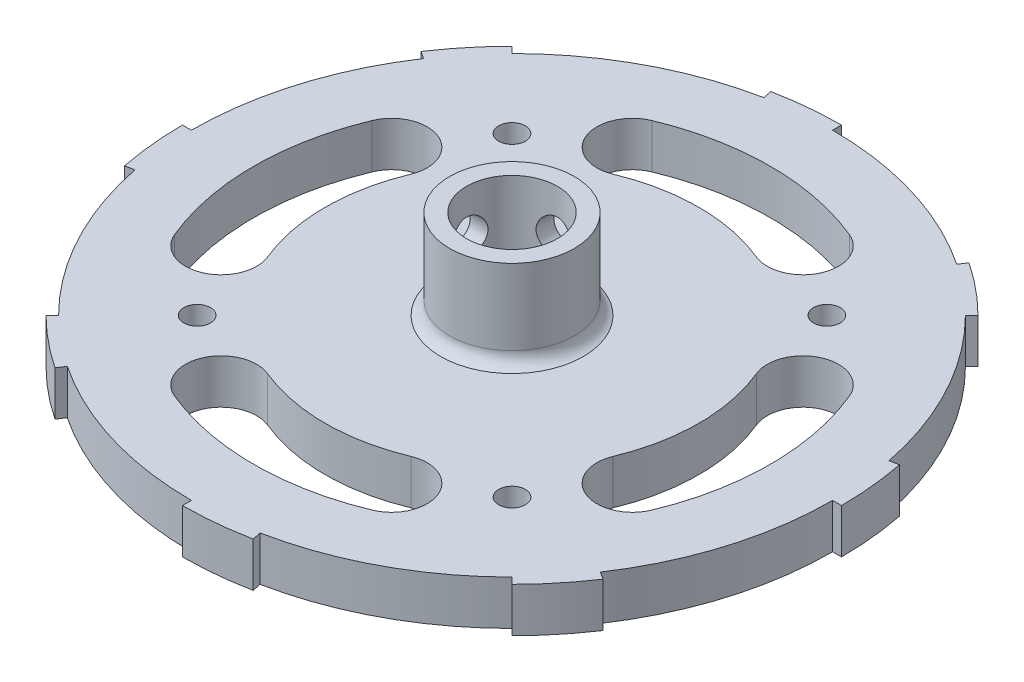
SolidWorks part; units mm, degrees
ref_plane "前视基准面" through (0, 0, 0) normal (0, 0, 1) x (1, 0, 0)
ref_plane "上视基准面" through (0, 0, 0) normal (0, 1, 0) x (1, 0, 0)
ref_plane "右视基准面" through (0, 0, 0) normal (1, 0, 0) x (0, 0, -1)
other "Configuration Table"
sketch "草图1" plane through (0, 0, 0) normal (0, 1, 0) x (1, 0, 0)
  circle A0 centre (0, 0) radius 37
  dimension "D1" = 74
extrude "凸台-拉伸1" add sketch "草图1" along normal blind 40
sketch "草图2" plane through (0, 40, 0) normal (0, 1, 0) x (1, 0, 0)
  circle A0 centre (0, 0) radius 5.1
  dimension "D1" = 10.2
extrude "切除-拉伸1" cut sketch "草图2" against normal blind 40
sketch "草图3" plane through (0, 40, 0) normal (0, 1, 0) x (1, 0, 0)
  line L0 (-1000, 0) -> (49000, 0) construction
  line L1 (0, -1000) -> (0, 49000) construction
  circle A0 centre (0, 0) radius 30
  circle A1 centre (0, 30) radius 5
  circle A3 centre (25.9808, 15) radius 5
  circle A4 centre (30, 0) radius 5
  circle A5 centre (25.9808, -15) radius 5
  circle A7 centre (0, -30) radius 5
  circle A8 centre (-15, -25.9808) radius 5
  circle A9 centre (-25.9808, -15) radius 5
  circle A11 centre (-25.9808, 15) radius 5
  circle A12 centre (-15, 25.9808) radius 5
  circle A13 centre (0, 0) radius 25
  circle A14 centre (0, 0) radius 35
  circle A15 centre (-30, 0) radius 5 [skipped]
  circle A16 centre (15, -25.9808) radius 5 [skipped]
  circle A17 centre (15, 25.9808) radius 5 [skipped]
  point P34 (0, 0)
  dimension "D1" = 60
  dimension "D2" = 10
  dimension "D3" = 12
extrude "切除-拉伸2" cut sketch "草图3" against normal blind 40 contours A0 A11 | A0 A11 | A13 A12 A0 A11 | A12 A14 A11 A0 | A0 A12 | A0 A12 | A1 A14 A12 A0 | A13 A1 A0 A12 | A0 A1 | A0 A1 | A0 A9 | A0 A9 | A9 A14 A8 A0 | A13 A9 A0 A8 | A0 A8 | A0 A8 | A8 A14 A7 A0 | A13 A8 A0 A7 | A0 A7 | A0 A7 | A0 A5 | A0 A5 | A0 A4 | A0 A4 | A0 A3 | A0 A3 | A4 A14 A3 A0 | A13 A4 A0 A3 | A13 A5 A0 A4 | A5 A14 A4 A0 region at (27.8047, 40, 0) region at (32.0453, 40, 0) region at (26.1943, 40, -7.0188) region at (31.6944, 40, -8.4925) region at (31.6944, 40, 8.4925) region at (26.1943, 40, 7.0188) region at (24.0795, 40, -13.9023) region at (27.752, 40, -16.0226) region at (27.752, 40, 16.0226) region at (24.0795, 40, 13.9023) region at (-7.0188, 40, -26.1943) region at (0, 40, -27.8047) region at (0, 40, -32.0453) region at (-8.4925, 40, -31.6944) region at (-8.4925, 40, 31.6944) region at (0, 40, 32.0453) region at (0, 40, 27.8047) region at (-7.0188, 40, 26.1943) region at (-19.1756, 40, -19.1756) region at (-13.9023, 40, -24.0795) region at (-16.0226, 40, -27.752) region at (-23.2019, 40, -23.2019) region at (-23.2019, 40, 23.2019) region at (-16.0226, 40, 27.752) region at (-13.9023, 40, 24.0795) region at (-19.1756, 40, 19.1756) region at (-24.0795, 40, -13.9023) region at (-27.752, 40, -16.0226) region at (-27.752, 40, 16.0226) region at (-24.0795, 40, 13.9023)
sketch "草图4" plane through (0, 40, 0) normal (0, 1, 0) x (1, 0, 0)
  circle A0 centre (0, 0) radius 7
  circle A1 centre (0, 0) radius 5.1
  dimension "D1" = 14
extrude "凸台-拉伸2" add sketch "草图4" along normal mid plane 20
sketch "草图5" plane through (0, 0, 0) normal (0, -1, 0) x (1, 0, 0)
  circle A0 centre (0, 0) radius 5.1
sketch "草图6" plane through (0, 0, 0) normal (0, 0, 1) x (1, 0, 0)
  line L0 (0, 50) -> (0, 45)
  line L1 (5.1, 50) -> (-5.1, 50) construction
  circle A0 centre (0, 45) radius 2
  dimension "D2" = 4
  dimension "D1" = 5
extrude "切除-拉伸3" cut sketch "草图6" against normal up to next contours A0 region at (-1.3742, 43.6258, 0)
sketch "草图7" plane through (0, 0, 0) normal (1, 0, 0) x (0, 0, -1)
  line L0 (0, 50) -> (0, 45)
  line L1 (7, 50) -> (-7, 50) construction
  circle A0 centre (0, 45) radius 2
  dimension "D2" = 4
  dimension "D1" = 5
extrude "切除-拉伸4" cut sketch "草图7" against normal up to next contours A0 region at (0, 43.6258, 1.3742)
sketch "草图10" plane through (0, 0, 0) normal (0, -1, 0) x (1, 0, 0)
  line L0 (0, 0) -> (0, 37)
  line L1 (0, 0) -> (7.2183, 36.2891)
  line L2 (0, 0) -> (14.1593, 34.1835)
  line L3 (0, 0) -> (20.5561, 30.7644)
  line L4 (0, 0) -> (26.163, 26.163)
  line L5 (0, 0) -> (30.7644, 20.5561)
  line L6 (0, 0) -> (34.1835, 14.1593)
  line L7 (0, 0) -> (36.2891, 7.2183)
  line L8 (0, 0) -> (37, 0)
  line L9 (0, 0) -> (36.2891, -7.2183)
  line L10 (0, 0) -> (34.1835, -14.1593)
  line L11 (0, 0) -> (30.7644, -20.5561)
  line L12 (0, 0) -> (26.163, -26.163)
  line L13 (0, 0) -> (20.5561, -30.7644)
  line L14 (0, 0) -> (14.1593, -34.1835)
  line L15 (0, 0) -> (7.2183, -36.2891)
  line L16 (0, 0) -> (0, -37)
  line L17 (0, 0) -> (-7.2183, -36.2891)
  line L18 (0, 0) -> (-14.1593, -34.1835)
  line L19 (0, 0) -> (-20.5561, -30.7644)
  line L20 (0, 0) -> (-26.163, -26.163)
  line L21 (0, 0) -> (-30.7644, -20.5561)
  line L22 (0, 0) -> (-34.1835, -14.1593)
  line L23 (0, 0) -> (-36.2891, -7.2183)
  line L24 (0, 0) -> (-37, 0)
  line L25 (0, 0) -> (-36.2891, 7.2183)
  line L26 (0, 0) -> (-34.1835, 14.1593)
  line L27 (0, 0) -> (-30.7644, 20.5561)
  line L28 (0, 0) -> (-26.163, 26.163)
  line L29 (0, 0) -> (-20.5561, 30.7644)
  line L30 (0, 0) -> (-14.1593, 34.1835)
  line L31 (0, 0) -> (-7.2183, 36.2891)
  circle A0 centre (0, 0) radius 37
  circle A1 centre (0, 0) radius 36
  point P38 (0, 0)
  circle M14 centre (0, 0) radius 37
  dimension "D1" = 72
  dimension "D2" = 37
  dimension "D3" = 32
extrude "切除-拉伸7" cut sketch "草图10" against normal up to next contours A1 L26 L25 M14 | A1 L27 L26 M14 | A1 L28 L27 M14 | A1 L30 L29 M14 | A1 L31 L30 M14 | A1 L0 L31 M14 | A1 L2 L1 M14 | A1 L3 L2 M14 | A1 L4 L3 M14 | A1 L6 L5 M14 | A1 L7 L6 M14 | A1 L8 L7 M14 | A1 L10 L9 M14 | A1 L11 L10 M14 | A1 L12 L11 M14 | A1 L14 L13 M14 | A1 L15 L14 M14 | A1 L16 L15 M14 | A1 L18 L17 M14 | A1 L19 L18 M14 | A1 L20 L19 M14 | A1 L22 L21 M14 | A1 L23 L22 M14 | A1 L24 L23 M14 region at (-3.5721, 0, 36.2682) region at (10.579, 0, 34.8744) region at (17.1794, 0, 32.1405) region at (23.1196, 0, 28.1713) region at (32.1405, 0, 17.1794) region at (34.8744, 0, 10.579) region at (36.2682, 0, 3.5721) region at (34.8744, 0, -10.579) region at (32.1405, 0, -17.1794) region at (28.1713, 0, -23.1196) region at (17.1794, 0, -32.1405) region at (10.579, 0, -34.8744) region at (3.5721, 0, -36.2682) region at (-10.579, 0, -34.8744) region at (-17.1794, 0, -32.1405) region at (-23.1196, 0, -28.1713) region at (-32.1405, 0, -17.1794) region at (-34.8744, 0, -10.579) region at (-36.2682, 0, -3.5721) region at (-34.8744, 0, 10.579) region at (-32.1405, 0, 17.1794) region at (-28.1713, 0, 23.1196) region at (-17.1794, 0, 32.1405) region at (-10.579, 0, 34.8744)
sketch "草图14" plane through (0, 40, 0) normal (0, 1, 0) x (1, 0, 0)
  circle A0 centre (0, 0) radius 36
extrude "凸台-拉伸4" add sketch "草图14" against normal blind 40
sketch "草图15" plane through (0, 40, 0) normal (0, 1, 0) x (1, 0, 0)
  circle A0 centre (0, 0) radius 25
  circle A1 centre (0, 25) radius 5
  circle A2 centre (12.5, 21.6506) radius 5
  circle A3 centre (21.6506, 12.5) radius 5
  circle A4 centre (25, 0) radius 5
  circle A5 centre (21.6506, -12.5) radius 5
  circle A6 centre (12.5, -21.6506) radius 5
  circle A7 centre (0, -25) radius 5
  circle A8 centre (-12.5, -21.6506) radius 5
  circle A9 centre (-21.6506, -12.5) radius 5
  circle A10 centre (-25, 0) radius 5
  circle A11 centre (-21.6506, 12.5) radius 5
  circle A12 centre (-12.5, 21.6506) radius 5
  circle A13 centre (0, 0) radius 30
  circle A14 centre (0, 0) radius 20
  point P30 (0, 0)
  dimension "D1" = 50
  dimension "D2" = 10
  dimension "D3" = 12
extrude "切除-拉伸11" cut sketch "草图15" against normal blind 40 contours A14 A12 A0 A11 | A12 A13 A11 A0 | A0 A11 | A0 A11 | A0 A12 | A0 A12 | A0 A1 | A0 A1 | A2 A13 A1 A0 | A14 A2 A0 A1 | A0 A2 | A0 A2 | A0 A3 | A0 A3 | A14 A4 A0 A3 | A4 A13 A3 A0 | A0 A4 | A0 A4 | A0 A5 | A0 A5 | A0 A6 | A0 A6 | A14 A6 A0 A5 | A6 A13 A5 A0 | A0 A7 | A0 A7 | A0 A8 | A0 A8 | A8 A13 A7 A0 | A14 A8 A0 A7 | A0 A9 | A0 A9 | A14 A10 A0 A9 | A10 A13 A9 A0 | A0 A10 | A0 A10 region at (22.7904, 40, 0) region at (27.0295, 40, 0) region at (21.2179, 40, -5.6853) region at (27.0803, 40, -7.2562) region at (19.7371, 40, -11.3952) region at (23.4082, 40, -13.5147) region at (23.4082, 40, 13.5147) region at (19.7371, 40, 11.3952) region at (19.8242, 40, 19.8242) region at (15.5326, 40, 15.5326) region at (11.3952, 40, -19.7371) region at (13.5147, 40, -23.4082) region at (5.6853, 40, -21.2179) region at (7.2562, 40, -27.0803) region at (13.5147, 40, 23.4082) region at (11.3952, 40, 19.7371) region at (0, 40, -22.7904) region at (0, 40, -27.0295) region at (-7.2562, 40, 27.0803) region at (0, 40, 27.0295) region at (0, 40, 22.7904) region at (-5.6853, 40, 21.2179) region at (-15.5326, 40, -15.5326) region at (-11.3952, 40, -19.7371) region at (-13.5147, 40, -23.4082) region at (-19.8242, 40, -19.8242) region at (-13.5147, 40, 23.4082) region at (-11.3952, 40, 19.7371) region at (-19.7371, 40, -11.3952) region at (-23.4082, 40, -13.5147) region at (-27.0803, 40, 7.2562) region at (-23.4082, 40, 13.5147) region at (-19.7371, 40, 11.3952) region at (-21.2179, 40, 5.6853) region at (-22.7904, 40, 0) region at (-27.0295, 40, 0)
sketch "草图17" plane through (0, 40, 0) normal (0, 1, 0) x (1, 0, 0)
  circle A0 centre (0, 0) radius 5.1
extrude "切除-拉伸12" cut sketch "草图17" against normal blind 40
ref_plane "基准面2" through (0, 20, 0) normal (0, 1, 0) x (1, 0, 0)
sketch "草图18" plane through (0, 20, 0) normal (0, 1, 0) x (1, 0, 0)
  line L0 (-27.5, 0) -> (27.5, 0) construction
  circle A0 centre (0, 0) radius 37
  circle A1 centre (0, 0) radius 10
  dimension "D1" = 20
sketch "草图20" plane through (0, 0, 0) normal (0, 0, 1) x (1, 0, 0)
  line L0 (-7, 40) -> (-7, 41.5)
  line L2 (-7, 43.0001) -> (-7, 40) construction
  line L3 (0, 40) -> (-20.0005, 40) construction
  line L4 (-8.0182, 40) -> (-7, 40)
  line L5 (0, -950) -> (0, 49050) construction
  line L6 (7, 50) -> (-7, 50) construction
  arc A0 (-7, 41.5) -> (-8.0182, 40) centre (-8.6141, 41.5) cw
  point P14 (0, 50)
revolve "旋转1" add sketch "草图20" angle 360 about L5
sketch "草图21" plane through (0, 0, 0) normal (0, -1, 0) x (1, 0, 0)
  circle A0 centre (0, 0) radius 37
extrude "切除-拉伸14" cut sketch "草图21" against normal blind 35
sketch "草图23" plane through (0, 35, 0) normal (0, -1, 0) x (1, 0, 0)
  circle A0 centre (0, 0) radius 5.1
  circle A1 centre (0, 0) radius 30
extrude "凸台-拉伸5" add sketch "草图23" against normal blind 5
sketch "草图24" plane through (0, 35, 0) normal (0, -1, 0) x (1, 0, 0)
  circle A0 centre (0, 0) radius 25
  circle A1 centre (0, 25) radius 4
  circle A2 centre (9.5671, 23.097) radius 4
  circle A3 centre (17.6777, 17.6777) radius 4
  circle A4 centre (23.097, 9.5671) radius 4
  circle A5 centre (25, 0) radius 4
  circle A6 centre (23.097, -9.5671) radius 4
  circle A7 centre (17.6777, -17.6777) radius 4
  circle A8 centre (9.5671, -23.097) radius 4
  circle A9 centre (0, -25) radius 4
  circle A10 centre (-9.5671, -23.097) radius 4
  circle A11 centre (-17.6777, -17.6777) radius 4
  circle A12 centre (-23.097, -9.5671) radius 4
  circle A13 centre (-25, 0) radius 4
  circle A14 centre (-23.097, 9.5671) radius 4
  circle A15 centre (-17.6777, 17.6777) radius 4
  circle A16 centre (-9.5671, 23.097) radius 4
  circle A17 centre (0, 0) radius 29
  circle A18 centre (0, 0) radius 21
  point P37 (0, 0)
  dimension "D1" = 50
  dimension "D2" = 8
  dimension "D3" = 16
extrude "切除-拉伸15" cut sketch "草图24" against normal blind 5 contours A0 A16 | A0 A16 | A18 A1 A0 A16 | A1 A17 A16 A0 | A0 A1 | A0 A1 | A18 A2 A0 A1 | A2 A17 A1 A0 | A0 A2 | A0 A2 | A0 A4 | A0 A4 | A18 A5 A0 A4 | A5 A17 A4 A0 | A0 A5 | A0 A5 | A18 A6 A0 A5 | A6 A17 A5 A0 | A0 A6 | A0 A6 | A0 A8 | A0 A8 | A0 A9 | A0 A9 | A18 A9 A0 A8 | A9 A17 A8 A0 | A18 A10 A0 A9 | A10 A17 A9 A0 | A0 A10 | A0 A10 | A0 A12 | A0 A12 | A13 A17 A12 A0 | A18 A13 A0 A12 | A0 A13 | A0 A13 | A18 A14 A0 A13 | A14 A17 A13 A0 | A0 A14 | A0 A14 region at (23.246, 35, 0) region at (26.6387, 35, 0) region at (22.0448, 35, 4.385) region at (26.995, 35, 5.3696) region at (26.995, 35, -5.3696) region at (22.0448, 35, -4.385) region at (21.4765, 35, 8.8959) region at (24.611, 35, 10.1942) region at (24.611, 35, -10.1942) region at (21.4765, 35, -8.8959) region at (4.385, 35, 22.0448) region at (8.8959, 35, 21.4765) region at (10.1942, 35, 24.611) region at (5.3696, 35, 26.995) region at (5.3696, 35, -26.995) region at (10.1942, 35, -24.611) region at (8.8959, 35, -21.4765) region at (4.385, 35, -22.0448) region at (-4.385, 35, 22.0448) region at (0, 35, 23.246) region at (0, 35, 26.6387) region at (-5.3696, 35, 26.995) region at (-5.3696, 35, -26.995) region at (0, 35, -26.6387) region at (0, 35, -23.246) region at (-4.385, 35, -22.0448) region at (-8.8959, 35, 21.4765) region at (-10.1942, 35, 24.611) region at (-10.1942, 35, -24.611) region at (-8.8959, 35, -21.4765) region at (-22.0448, 35, 4.385) region at (-21.4765, 35, 8.8959) region at (-24.611, 35, 10.1942) region at (-26.995, 35, 5.3696) region at (-26.995, 35, -5.3696) region at (-24.611, 35, -10.1942) region at (-21.4765, 35, -8.8959) region at (-22.0448, 35, -4.385) region at (-23.246, 35, 0) region at (-26.6387, 35, 0)
sketch "草图25" plane through (0, 35, 0) normal (0, -1, 0) x (1, 0, 0)
  circle A0 centre (0, 0) radius 25
  circle A1 centre (0, 25) radius 1.5
  circle A2 centre (9.5671, 23.097) radius 1.5
  circle A3 centre (17.6777, 17.6777) radius 1.5
  circle A4 centre (23.097, 9.5671) radius 1.5
  circle A5 centre (25, 0) radius 1.5
  circle A6 centre (23.097, -9.5671) radius 1.5
  circle A7 centre (17.6777, -17.6777) radius 1.5
  circle A8 centre (9.5671, -23.097) radius 1.5
  circle A9 centre (0, -25) radius 1.5
  circle A10 centre (-9.5671, -23.097) radius 1.5
  circle A11 centre (-17.6777, -17.6777) radius 1.5
  circle A12 centre (-23.097, -9.5671) radius 1.5
  circle A13 centre (-25, 0) radius 1.5
  circle A14 centre (-23.097, 9.5671) radius 1.5
  circle A15 centre (-17.6777, 17.6777) radius 1.5
  circle A16 centre (-9.5671, 23.097) radius 1.5
  point P39 (0, 0)
  dimension "D1" = 3
  dimension "D2" = 16
extrude "切除-拉伸16" cut sketch "草图25" against normal blind 5 contours A0 A15 | A0 A15 | A3 | A7 | A11 region at (-17.2218, 35, 17.2218) region at (-18.122, 35, 18.122)
sketch "草图26" plane through (0, 35, 0) normal (0, -1, 0) x (1, 0, 0)
  line L0 (-17.6777, 17.6777) -> (-17.6777, 20.1777)
  line L1 (-1000, 0) -> (49000, 0) construction
  line L2 (0, -1000) -> (0, 49000) construction
  circle A0 centre (-17.6777, 17.6777) radius 2.5
  circle A1 centre (-17.6777, 20.1777) radius 0.5
  circle A2 centre (-15.1777, 17.6777) radius 0.5
  circle A3 centre (-17.6777, 15.1777) radius 0.5
  circle A4 centre (-20.1777, 17.6777) radius 0.5
  circle A5 centre (-15.1777, -17.6777) radius 0.5
  circle A6 centre (-20.1777, -17.6777) radius 0.5
  circle A7 centre (-17.6777, -15.1777) radius 0.5
  circle A8 centre (-17.6777, -20.1777) radius 0.5
  circle A9 centre (20.1777, -17.6777) radius 0.5
  circle A10 centre (17.6777, -20.1777) radius 0.5
  circle A11 centre (15.1777, -17.6777) radius 0.5
  circle A12 centre (17.6777, -15.1777) radius 0.5
  circle A13 centre (15.1777, 17.6777) radius 0.5
  circle A14 centre (17.6777, 15.1777) radius 0.5
  circle A15 centre (17.6777, 20.1777) radius 0.5
  circle A16 centre (20.1777, 17.6777) radius 0.5
  dimension "D1" = 5
  dimension "D2" = 4
extrude "切除-拉伸18" cut sketch "草图26" against normal blind 2 contours A4 | A1 | A3 | A2 | A7 | A6 | A8 | A5 | A9 | A11 | A10 | A12 | A15 | A13 | A14 | A16
